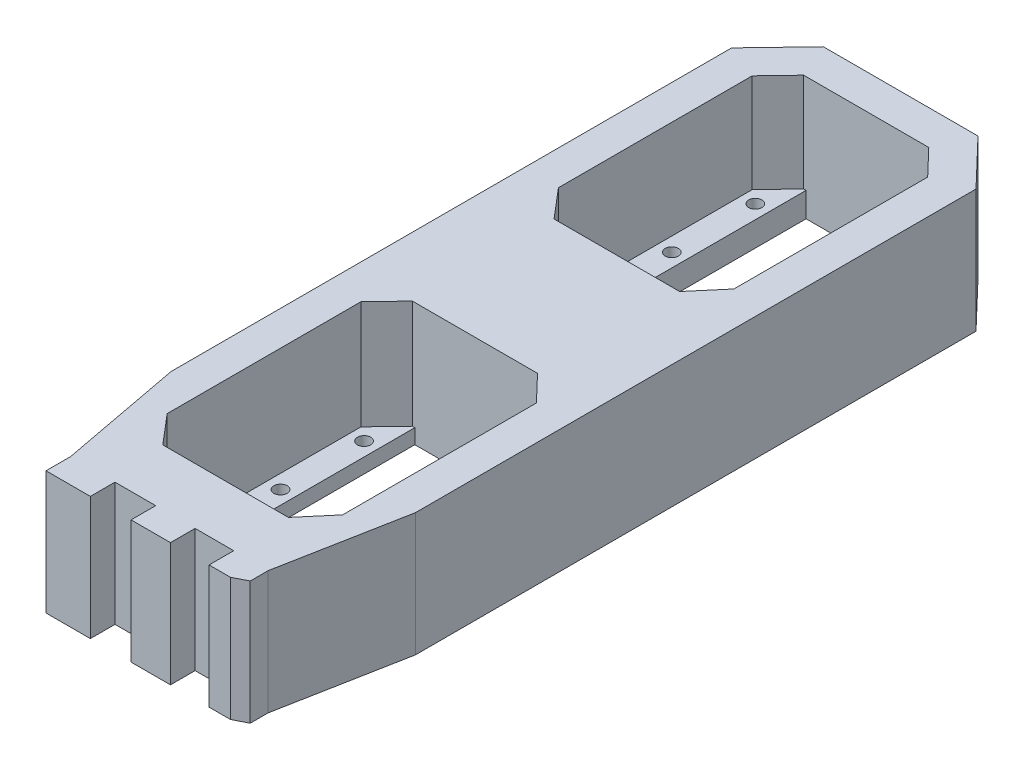
SolidWorks part; units mm, degrees
material "ABS"
ref_plane "Płaszczyzna przednia" through (0, 0, 0) normal (0, 0, 1) x (1, 0, 0)
ref_plane "Płaszczyzna górna" through (0, 0, 0) normal (0, 1, 0) x (1, 0, 0)
ref_plane "Płaszczyzna prawa" through (0, 0, 0) normal (1, 0, 0) x (0, 0, -1)
sketch "Szkic1" plane through (0, 0, 0) normal (0, 1, 0) x (1, 0, 0)
  line L0 (-12.6522, 196.7963) -> (11.7478, 196.7963)
  line L1 (-0.4522, 314.1963) -> (-0.4522, 55.3963) construction
  line L2 (-37.6655, 184.7963) -> (36.761, 184.7963) construction
  line L3 (11.7478, 196.7963) -> (11.7478, 151.7963)
  line L4 (19.5956, 55.3963) -> (-20.5, 55.3963)
  line L5 (11.7478, 151.7963) -> (-12.6522, 151.7963)
  line L6 (24.3478, 126.118) -> (24.3478, 80.5335)
  line L7 (-13.1522, 196.7963) -> (12.2478, 196.7963)
  line L8 (-25.2522, 184.7963) -> (24.3478, 184.7963) construction
  line L9 (-12.6522, 117.3963) -> (11.7478, 117.3963)
  line L10 (-25.2522, 131.7671) -> (-25.2522, 126.118)
  line L11 (17.3478, 191.4706) -> (17.3478, 152.1401)
  line L12 (-37.6655, 105.3963) -> (36.761, 105.3963) construction
  line L13 (17.3478, 152.1401) -> (12.2956, 146.1963)
  line L14 (11.7478, 117.3963) -> (11.7478, 72.3963)
  line L15 (11.7478, 72.3963) -> (-12.6522, 72.3963)
  line L16 (24.3478, 149.5671) -> (24.3478, 131.7671)
  line L17 (-13.1522, 117.3963) -> (12.2478, 117.3963)
  line L18 (-25.2522, 105.3963) -> (24.3478, 105.3963) construction
  line L19 (1.0907, -6.7501) -> (1.0723, -6.7223)
  line L20 (17.3478, 112.0706) -> (17.3478, 72.7401)
  line L21 (-25.2522, 149.5671) -> (-25.2522, 131.7671)
  line L22 (24.3478, 131.7671) -> (24.3478, 126.118)
  line L23 (12.2956, 146.1963) -> (-13.2, 146.1963)
  line L24 (12.2478, 196.7963) -> (17.3478, 191.4706)
  line L25 (17.3478, 72.7401) -> (12.2956, 66.7963)
  line L26 (-13.1522, 196.7963) -> (-18.2522, 191.4706)
  line L27 (12.2956, 66.7963) -> (-13.2, 66.7963)
  line L28 (12.2478, 117.3963) -> (17.3478, 112.0706)
  line L29 (-13.1522, 117.3963) -> (-18.2522, 112.0706)
  line L30 (-18.2522, 72.7401) -> (-13.2, 66.7963)
  line L31 (-18.2522, 112.0706) -> (-18.2522, 72.7401)
  line L32 (-12.6522, 117.3963) -> (-12.6522, 72.3963)
  line L33 (19.5956, 55.3963) -> (24.3478, 80.5335)
  line L34 (-18.2522, 152.1401) -> (-13.2, 146.1963)
  line L35 (-18.2522, 191.4706) -> (-18.2522, 152.1401)
  line L36 (1.1229, -6.7586) -> (1.0907, -6.7501)
  line L37 (-12.6522, 196.7963) -> (-12.6522, 151.7963)
  line L38 (-20.5, 55.3963) -> (-25.2522, 80.5335)
  line L39 (-25.2522, 126.118) -> (-25.2522, 80.5335)
  line L44 (15.2364, 203.7963) -> (24.3478, 194.2818)
  line L45 (24.3478, 194.2818) -> (24.3478, 149.5671)
  line L46 (-2.1229, -6.7586) -> (-2.0907, -6.7501)
  line L47 (24.3478, 149.5671) -> (15.5327, 139.1963)
  line L48 (15.5327, 139.1963) -> (-16.4371, 139.1963)
  line L49 (-25.2522, 149.5671) -> (-16.4371, 139.1963)
  line L50 (-25.2522, 194.2818) -> (-25.2522, 149.5671)
  line L51 (-16.1409, 203.7963) -> (-25.2522, 194.2818)
  line L52 (-16.1409, 203.7963) -> (15.2364, 203.7963)
  circle A0 centre (14.5478, 109.8963) radius 1.35
  circle A1 centre (-0.4522, 105.3963) radius 4
  circle A2 centre (14.5, 92.8963) radius 1.35
  circle A3 centre (14.5, 75.8963) radius 1.35
  circle A4 centre (8.0478, 69.5963) radius 1.35
  circle A5 centre (-8.9522, 69.5963) radius 1.35
  circle A6 centre (14.5478, 189.2963) radius 1.35
  circle A7 centre (-15.4044, 75.8963) radius 1.35
  circle A8 centre (-15.4044, 92.8963) radius 1.35
  circle A9 centre (-15.4522, 109.8963) radius 1.35
  circle A10 centre (-0.4522, 184.7963) radius 4
  circle A11 centre (14.5, 172.2963) radius 1.35
  circle A12 centre (14.5, 155.2963) radius 1.35
  circle A13 centre (8.0478, 148.9963) radius 1.35
  circle A14 centre (-8.9522, 148.9963) radius 1.35
  circle A15 centre (-15.4044, 155.2963) radius 1.35
  circle A16 centre (-15.4044, 172.2963) radius 1.35
  circle A17 centre (-15.4522, 189.2963) radius 1.35
  point P9 (-15.5208, -48.1484)
  point P14 (-0.4522, 156.3785)
  point P18 (-34.2569, 59.805)
  point P22 (-0.4522, 105.3963)
  point P27 (32.5, 54.0178)
  point P34 (-0.4522, 105.3963)
  point P41 (-0.4522, 148.8753)
  point P44 (-0.4522, 211.3963)
  point P45 (-9.988, 152.4054)
  point P47 (-36.488, 132.4054)
  point P71 (-0.4522, 66.7963)
  point P73 (-0.4522, 72.3963)
  point P74 (-0.4522, 117.3963)
  point P80 (-0.4522, 143.7963)
  point P101 (-0.4522, 146.1963)
  point P103 (-0.4522, 151.7963)
  point P104 (-0.4522, 196.7963)
  dimension "D6" = 45
  dimension "D5" = 12.2
  dimension "D8" = 2.7
  dimension "D4" = 50
  dimension "D12" = 12.2
  dimension "D13" = 9.3
  dimension "D14" = 7.5
  dimension "D15" = 8
  dimension "D16" = 7
  dimension "D17" = 1.0907
  dimension "D10" = 8
  dimension "D21" = 12.2478
  dimension "D26" = 7.5
  dimension "D27" = 2.8
  dimension "D35" = 24.5
  dimension "D24" = 12.2956
  dimension "D29" = 2.0907
  dimension "D30" = 55.3963
  dimension "D31" = 2.7
  dimension "D22" = 2.7
  dimension "D32" = 2.7
  dimension "D34" = 2.7
  dimension "D11" = 11.7478
  dimension "D18" = 1.1229
  dimension "D19" = 45
  dimension "D20" = 12
  dimension "D23" = 8.0478
  dimension "D25" = 14.5
  dimension "D28" = 19.5956
  dimension "D33" = 72.7401
  dimension "D36" = 24.5
  dimension "D37" = 41.5
  dimension "D38" = 47.8
  dimension "D39" = 5.3257
  dimension "D40" = 41.5
  dimension "D41" = 80.5335
  dimension "D42" = 47.8
  dimension "D43" = 9.3
  dimension "D44" = 5.3257
  dimension "D45" = 7
  dimension "D46" = 126.118
  dimension "D47" = 131.7671
  dimension "D49" = 148.8753
  dimension "D51" = 211.3963
  dimension "D52" = 6.7223
  dimension "D53" = 6.7501
  dimension "D54" = 6.7586
  dimension "D7" = 12
extrude "Dodanie-wyciągnięcie1" add sketch "Szkic1" along normal blind 5 contours L4 L6 | L37 L7 L26 L35 L34 L23 L13 L11 L24 L3 L5 A16 A14 A13 A12 A11 A6 A15 A17 | L52 L51 L50 L49 L48 L47 L45 L44 L35 L26 L7 L0 L24 L11 L13 L23 L34 region at (-13.2709, 0, -174.2963) region at (-0.4522, 0, -56.4607) region at (19.3197, 0, -144.9092)
extrude "Dodanie-wyciągnięcie2" add sketch "Szkic1<3>" along normal blind 25 contours L4 L6 | L52 L51 L50 L49 L48 L47 L45 L44 L35 L26 L7 L0 L24 L11 L13 L23 L34 region at (-0.4522, 0, -56.4607) region at (19.3197, 0, -144.9092)
sketch "Szkic1<3>" plane through (0, 0, 0) normal (0, 1, 0) x (1, 0, 0) same geometry as "Szkic1"
sketch "Szkic8" plane through (0, 25, 0) normal (0, 1, 0) x (1, 0, 0)
  line L0 (19.5956, 55.3963) -> (19.5956, 51.7445)
  line L1 (16.9256, 50.3963) -> (12.5956, 50.3963)
  line L2 (12.5956, 50.3963) -> (12.5956, 55.3963)
  line L3 (19.5956, 55.3963) -> (-20.5, 55.3963) construction
  line L4 (12.5956, 55.3963) -> (4.7588, 55.3963)
  line L5 (4.7588, 55.3963) -> (4.7588, 50.3963)
  line L6 (4.7588, 50.3963) -> (-3.2412, 50.3963)
  line L7 (-3.2412, 50.3963) -> (-3.2412, 55.3963)
  line L8 (-3.2412, 55.3963) -> (-11.5, 55.3963)
  line L9 (-11.5, 55.3963) -> (-11.5, 50.3963)
  line L10 (-11.5, 50.3963) -> (-20.5, 50.3963)
  line L11 (-20.5, 50.3963) -> (-20.5, 55.3963)
  line L12 (19.5956, 55.3963) -> (-20.5, 55.3963)
  line L13 (19.5956, 51.7445) -> (16.9256, 50.3963)
  line L22 (-16.1409, 203.7963) -> (-25.2522, 194.2818)
  line L23 (-16.1409, 203.7963) -> (-25.2522, 194.2818)
  line L24 (24.3478, 194.2818) -> (15.2364, 203.7963)
  line L25 (24.3478, 194.2818) -> (15.2364, 203.7963)
  line L26 (15.2364, 203.7963) -> (-16.1409, 203.7963)
  line L27 (15.2364, 203.7963) -> (-16.1409, 203.7963)
  line L34 (-25.2522, 194.2818) -> (-25.2522, 80.5335)
  line L36 (-25.2522, 80.5335) -> (-20.5, 55.3963)
  line L37 (-20.5, 55.3963) -> (19.5956, 55.3963)
  line L38 (19.5956, 55.3963) -> (24.3478, 80.5335)
  line L39 (24.3478, 80.5335) -> (24.3478, 194.2818)
  line L56 (-25.2522, 194.2818) -> (-25.2522, 80.5335)
  line L58 (-25.2522, 80.5335) -> (-20.5, 55.3963)
  line L60 (19.5956, 55.3963) -> (24.3478, 80.5335)
  line L61 (24.3478, 80.5335) -> (24.3478, 194.2818)
  point P1 (19.5956, 50.3963)
  line M75 (-20.5, 55.3963) -> (19.5956, 55.3963)
  dimension "D1" = 5
  dimension "D2" = 7
  dimension "D3" = 8
  dimension "D4" = 9
  dimension "D5" = 0
  dimension "D6" = 153.21
  dimension "D7" = 4.33
extrude "Dodanie-wyciągnięcie3" add sketch "Szkic8" against normal blind 25 contours L0 L12 L2 L1 | L5 L12 L7 L6 | L9 L12 L11 L10 | L13 L0 L2 L1 M75 region at (15.9541, 25, -53.0075) region at (0.7588, 25, -52.8963) region at (-16, 25, -52.8963)
extrude "Dodanie-wyciągnięcie4" add sketch "Szkic1<4>" along normal blind 3 contours L32 L17 L29 L31 L30 L27 L25 L20 L28 L14 L15 A8 A5 A4 A3 A2 A0 A7 A9 region at (-13.2709, 0, -94.8963)
sketch "Szkic1<4>" plane through (0, 0, 0) normal (0, 1, 0) x (1, 0, 0) same geometry as "Szkic1"
